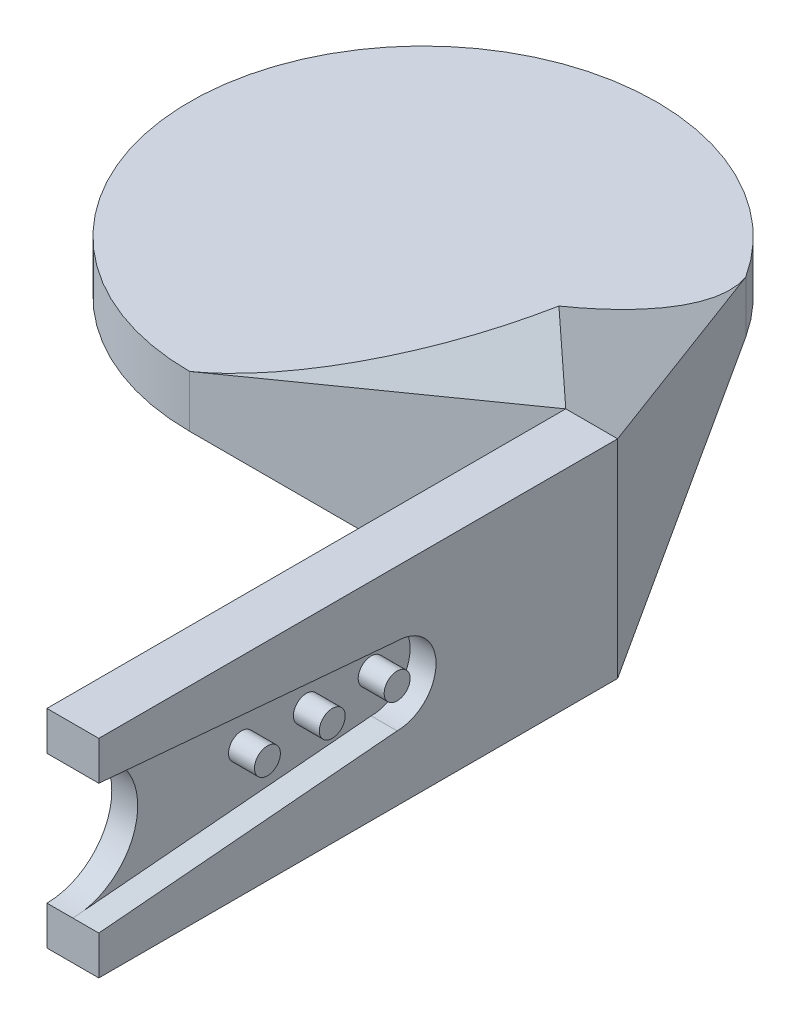
SolidWorks part; units mm, degrees
ref_plane "Front Plane" through (0, 0, 0) normal (0, 0, 1) x (1, 0, 0)
ref_plane "Top Plane" through (0, 0, 0) normal (0, 1, 0) x (1, 0, 0)
ref_plane "Right Plane" through (0, 0, 0) normal (1, 0, 0) x (0, 0, -1)
sketch "Sketch1" plane through (0, 0, 0) normal (0, 1, 0) x (1, 0, 0)
  line L0 (0, 0) -> (6.5, 0) construction
  line L1 (6.5, 1.5) -> (2, 1.5)
  line L2 (6.5, -1.5) -> (2, -1.5)
  line L3 (1.5, -6.5) -> (1.5, -2)
  line L4 (-1.5, -6.5) -> (-1.5, -2)
  line L5 (-6.5, -1.5) -> (-2, -1.5)
  line L6 (-6.5, 1.5) -> (-2, 1.5)
  line L7 (-1.5, 6.5) -> (-1.5, 2)
  line L8 (1.5, 6.5) -> (1.5, 2)
  line L9 (0, -9) -> (14.5, -9)
  line L11 (14.5, -9) -> (16.5, -9)
  line L13 (14.5, -9) -> (14.5, -29)
  line L14 (14.5, -29) -> (16.5, -29)
  line L15 (16.5, -29) -> (16.5, -9)
  line L16 (16.5, -9) -> (7.5669, 4.8726)
  circle A0 centre (0, 0) radius 1
  circle A1 centre (6.5, 0) radius 0.5
  circle A2 centre (0, 0) radius 2.5
  circle A4 centre (6.5, 0) radius 1.5
  circle A5 centre (0, -6.5) radius 1.5
  circle A6 centre (0, -6.5) radius 0.5
  circle A7 centre (-6.5, 0) radius 1.5
  circle A8 centre (-6.5, 0) radius 0.5
  circle A9 centre (0, 6.5) radius 1.5
  circle A10 centre (0, 6.5) radius 0.5
  circle A11 centre (0, 0) radius 9
  point P35 (0, 0)
  dimension "D1" = 4
extrude "Boss-Extrude1" add sketch "Sketch1" along normal blind 2 contours A10 | A8 | A6 | A1 | A0 | A0 A2 | A7 L5 A2 L6 | A7 A8 | A9 A10 | A9 L7 A2 L8 | A5 L3 A2 L4 | A2 L0 A4 L1 | L0 A2 L2 A4 | A4 A1 | A5 A6 | A11 A9 L8 A2 L1 A4 L2 L3 A5 L4 L5 A7 L6 L7 region at (2.3046, 0, 0.7682) region at (3.8465, 0, -0.8153) region at (3.8465, 0, 0.8153) region at (-0.9717, 0, 0) region at (6.5, 0, -0.4859) region at (5.4693, 0, -1.0307) region at (0, 0, -3.8465) region at (0, 0, 3.8465) region at (0, 0, -5.0424) region at (0, 0, 7.9576) region at (-3.8465, 0, 0) region at (-5.4693, 0, -1.0307) region at (-7.6776, 0, -4.1878) region at (0, 0, 6.5) region at (-6.5, 0, 0) region at (0, 0, -6.5)
extrude "Boss-Extrude2" add sketch "Sketch1<4>" along normal blind 8 contours A11 L9 | L11 | L14 L15 L11 L13 region at (10.2, 0, 5.5636) region at (15.5, 0, 19)
sketch "Sketch1<4>" plane through (0, 0, 0) normal (0, 1, 0) x (1, 0, 0) same geometry as "Sketch1"
extrude "Cut-Extrude1" cut sketch "Sketch1<5>" along normal blind 1 contours A5 A6 | A5 L3 A2 L4 | A7 L5 A2 L6 | A7 A8 | A0 A2 | A9 L7 A2 L8 | A9 A10 | A4 A1 | A2 L0 A4 L1 | L0 A2 L2 A4 | A0 region at (2.3046, 0, 0.7682) region at (3.8465, 0, -0.8153) region at (3.8465, 0, 0.8153) region at (-0.9717, 0, 0) region at (5.4693, 0, -1.0307) region at (0, 0, -3.8465) region at (0, 0, 3.8465) region at (0, 0, -5.0424) region at (0, 0, 7.9576) region at (-3.8465, 0, 0) region at (-5.4693, 0, -1.0307)
sketch "Sketch1<5>" plane through (0, 0, 0) normal (0, 1, 0) x (1, 0, 0) same geometry as "Sketch1"
sketch "Sketch2" plane through (0, 0, 9) normal (0, 0, 1) x (1, 0, 0)
  line L0 (0, 2) -> (14.5, 8)
  line L1 (14.5, 8) -> (0, 8)
  line L2 (0, 8) -> (0, 2)
extrude "Cut-Extrude2" cut sketch "Sketch2" against normal blind 9 contours L2 L0 L1
sketch "Sketch4" plane through (16.5, 0, 0) normal (1, 0, 0) x (0, 0, -1)
  line L0 (-29, 8) -> (-29, 0) construction
  line L1 (-29, 4) -> (-17.5, 4) construction
  line L2 (-29, 6.5) -> (-17.5, 5.5)
  line L3 (-17.5, 2.5) -> (-29, 1.5)
  line L4 (-17.5, 4) -> (-20.448, 4) construction
  line L5 (-29, 4) -> (-22.5, 4) construction
  line L6 (-17.5, 4) -> (-20, 4) construction
  circle A0 centre (-29, 4) radius 2.5
  circle A1 centre (-17.5, 4) radius 0.5
  circle A2 centre (-17.5, 4) radius 1.5
  circle A4 centre (-22.5, 4) radius 0.5
  circle A5 centre (-20, 4) radius 0.5
  line M7 (-29, 8) -> (-29, 0)
extrude "Cut-Extrude5" cut sketch "Sketch4" against normal blind 1 contours L3 A0 L2 M7 | A2 L2 A0 L3 A5 A4 | A2 A1 region at (16.5, 4, 27.9385) region at (16.5, 4, 23.1616) region at (16.5, 5.0307, 16.4693)
sketch "Sketch6" plane through (15.5, 0, 0) normal (1, 0, 0) x (0, 0, -1)
  line L0 (-29, 4) -> (-28.6355, 4) construction
  line L1 (-29, 6.5) -> (-29, 1.5) construction
  line L2 (-29, 4) -> (-29, 6.5) construction
  circle A0 centre (-29, 4) radius 2.5
extrude "Cut-Extrude6" cut sketch "Sketch6" against normal blind 10
sketch "Sketch8" plane through (16.5, 0, 0) normal (1, 0, 0) x (0, 0, -1)
  line L0 (-9, 8) -> (4.8726, 2)
  line L1 (4.8726, 2) -> (4.8726, 8)
  line L2 (4.8726, 8) -> (-9, 8)
extrude "Cut-Extrude8" cut sketch "Sketch8" against normal blind 10
